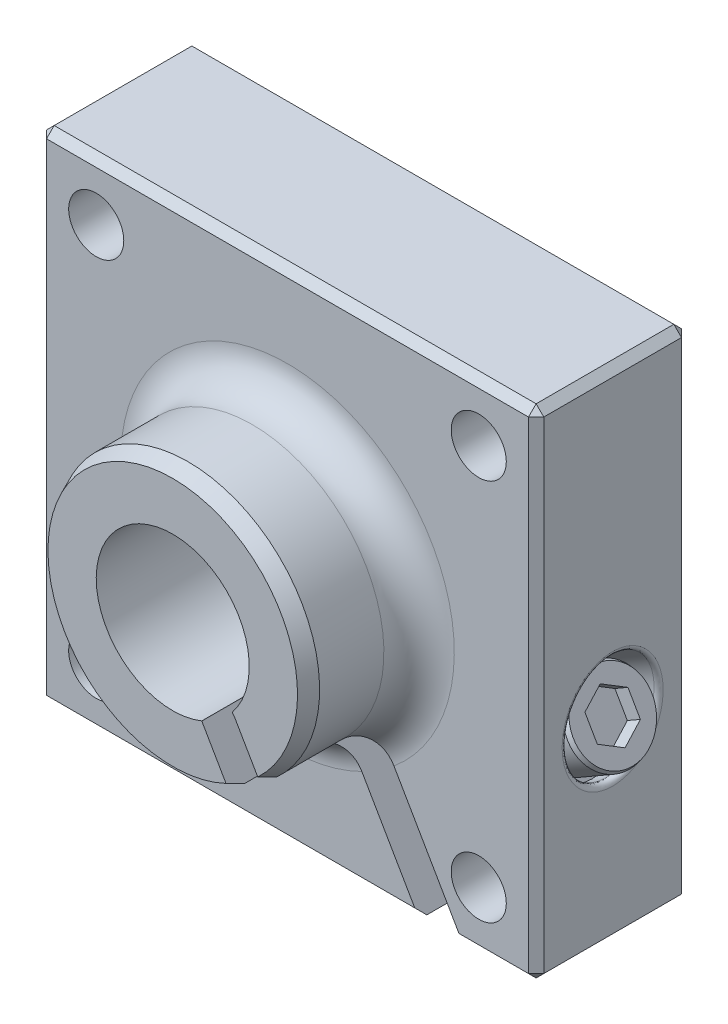
SolidWorks part; units mm, degrees
ref_plane "Front" through (0, 0, 0) normal (0, 0, 1) x (1, 0, 0)
ref_plane "Top" through (0, 0, 0) normal (0, 1, 0) x (1, 0, 0)
ref_plane "Right" through (0, 0, 0) normal (1, 0, 0) x (0, 0, -1)
sketch "Sketch1" plane through (0, 0, 0) normal (0, 0, 1) x (1, 0, 0)
  line L0 (-15.875, 0) -> (15.875, 0) construction
  line L1 (20.6375, -20.6375) -> (-20.6375, -20.6375)
  line L2 (20.6375, -20.6375) -> (20.6375, 20.6375)
  line L3 (20.6375, 20.6375) -> (-20.6375, 20.6375)
  line L4 (-20.6375, -20.6375) -> (-20.6375, 20.6375)
  line L5 (20.6375, -20.6375) -> (-20.6375, 20.6375) construction
  line L6 (20.6375, 20.6375) -> (-20.6375, -20.6375) construction
  line L7 (15.875, -15.875) -> (15.875, 15.875)
  line L8 (15.875, 15.875) -> (-15.875, 15.875)
  line L9 (-15.875, -15.875) -> (-15.875, 15.875)
  line L10 (15.875, -15.875) -> (-15.875, -15.875)
  circle A0 centre (15.875, 15.875) radius 2.286
  circle A1 centre (-15.875, 15.875) radius 2.286
  circle A2 centre (-15.875, -15.875) radius 2.286
  circle A3 centre (15.875, -15.875) radius 2.286
  circle A4 centre (0, 0) radius 6.35
  point P0 (0, 0)
  point P8 (0, 0)
  dimension "D1" = 4.7625
ref_plane "Plane1" through (0, 20.6375, 0) normal (0, 1, 0) x (1, 0, 0)
sketch "Sketch3" plane through (0, 20.6375, 0) normal (0, 1, 0) x (1, 0, 0)
  line L1 (20.6375, 0) -> (-20.6375, 0) construction
  line L2 (20.6375, 0) -> (20.6375, 12.7) construction
  line L3 (20.6375, 12.7) -> (-20.6375, 12.7) construction
  line L4 (-20.6375, 0) -> (-20.6375, 12.7) construction
  line L6 (20.6375, 12.7) -> (-20.6375, 0) construction
  line L8 (0, -9.525) -> (20.6375, -9.525) construction
  line L9 (0, 0) -> (0, -9.525) construction
  point P0 (0, 0)
  point P6 (0, 0)
  point P11 (0, -9.525)
  dimension "D1" = 41.275
sketch "Sketch4" plane through (0, 0, 0) normal (0, 0, 1) x (1, 0, 0)
  line L0 (20.6375, -20.6375) -> (20.6375, 20.6375) construction
  line L1 (20.6375, 20.6375) -> (-20.6375, 20.6375) construction
  line L2 (-20.6375, -20.6375) -> (-20.6375, 20.6375) construction
  line L3 (20.6375, -20.6375) -> (-20.6375, -20.6375) construction
  line L4 (20.6375, -20.6375) -> (20.6375, 20.6375)
  line L5 (20.6375, 20.6375) -> (-20.6375, 20.6375)
  line L6 (-20.6375, -20.6375) -> (-20.6375, 20.6375)
  line L7 (20.6375, -20.6375) -> (-20.6375, -20.6375)
  circle A0 centre (-15.875, -15.875) radius 2.286 construction
  circle A1 centre (15.875, -15.875) radius 2.286 construction
  circle A2 centre (15.875, 15.875) radius 2.286 construction
  circle A3 centre (-15.875, 15.875) radius 2.286 construction
  circle A4 centre (0, 0) radius 6.35 construction
  circle A5 centre (-15.875, -15.875) radius 2.286
  circle A6 centre (15.875, -15.875) radius 2.286
  circle A7 centre (15.875, 15.875) radius 2.286
  circle A8 centre (-15.875, 15.875) radius 2.286
  circle A9 centre (0, 0) radius 6.35
extrude "Boss-Extrude1" add sketch "Sketch4" against normal up to vertex (12.7 mm away) up to point (-20.6375, 20.6375, -12.7)
sketch "Sketch6" plane through (0, 0, 0) normal (0, 0, 1) x (1, 0, 0)
  line L4 (-20.6375, -20.6375) -> (20.6375, -20.6375)
  line L5 (20.6375, -20.6375) -> (20.6375, 20.6375)
  line L6 (20.6375, 20.6375) -> (-20.6375, 20.6375)
  line L7 (-20.6375, 20.6375) -> (-20.6375, -20.6375)
  line L8 (-20.6375, -20.6375) -> (20.6375, -20.6375)
  line L9 (20.6375, -20.6375) -> (20.6375, 20.6375)
  line L10 (20.6375, 20.6375) -> (-20.6375, 20.6375)
  line L11 (-20.6375, 20.6375) -> (-20.6375, -20.6375)
  circle A0 centre (0, 0) radius 6.35 construction
  circle A1 centre (0, 0) radius 6.35
  circle A2 centre (0, 0) radius 10.922
  circle M5 centre (0, 0) radius 6.35
  dimension "D2" = 4.572
extrude "Boss-Extrude2" add sketch "Sketch6" along normal up to vertex (9.525 mm away) contours A2 M5 region at (-10.6131, 0, 0) up to point (0, 20.6375, 9.525)
sketch "Sketch7" plane through (0, 0, 9.525) normal (0, 0, 1) x (1, 0, 0)
  line L0 (20.6375, -20.6375) -> (12.7635, -20.6375) construction
sketch "Sketch8" plane through (0, 0, 9.525) normal (0, 0, 1) x (1, 0, 0)
  line L0 (12.7635, -20.6375) -> (3.79, -5.0949) construction
  line L1 (20.6375, -20.6375) -> (-20.6375, -20.6375) construction
  line L2 (12.7635, -20.6375) -> (3.79, -5.0949) construction
  line L3 (11.3887, -21.4312) -> (2.4152, -5.8887)
  line L4 (14.1383, -19.8438) -> (5.1648, -4.3012)
  circle A0 centre (0, 0) radius 6.35 construction
  arc A1 (11.3887, -21.4312) -> (14.1383, -19.8438) centre (12.7635, -20.6375) ccw
  arc A2 (5.1648, -4.3012) -> (2.4152, -5.8887) centre (3.79, -5.0949) ccw
  point P7 (8.2767, -12.8662)
  point P12 (12.7635, -20.6375)
  dimension "D1" = 60
  dimension "D2" = 1.5875
  dimension "D3" = 7.874
extrude "Cut-Extrude1" cut sketch "Sketch8" against normal through all
chamfer "Chamfer1" distance 1.27 angle 24 1 edges at (-6.0915, 9.0655, 9.525) first distance on face at (-0.0325, 0.0484, 4.7625)
chamfer "Chamfer3" distance 0.635 angle 45 14 edges at (20.6375, 0, 0) (-20.6375, 20.6375, -6.35) (0, 20.6375, -12.7) (20.6375, 20.6375, -6.35) (-4.8535, -20.6375, -12.7) (-20.6375, 0, -12.7) (-20.6375, -20.6375, -6.35) (-20.6375, 0, 0) (0, 20.6375, 0) (17.4942, -20.6375, -12.7) (20.6375, 0, -12.7) (20.6375, -20.6375, -6.35) (-4.8535, -20.6375, 0) (17.4942, -20.6375, 0)
sketch "Sketch9" plane through (0, 0, 0) normal (0, 0, 1) x (1, 0, 0)
  line L0 (-20.0025, -20.6375) -> (20.6375, -20.6375) construction
  line L1 (4.3155, -13.7542) -> (20.6375, -4.3307) construction
  line L3 (20.6375, -0.9017) -> (20.6375, -7.7597)
  line L4 (20.6375, 20.0025) -> (20.6375, -20.0025) construction
  line L5 (20.6375, -7.7597) -> (20.0328, -7.7597) construction
  line L6 (20.6375, -6.4135) -> (20.6375, -2.2479) construction
  point P2 (20.6375, -4.3307)
  point P9 (20.6375, -0.9017)
  point P14 (39.6875, 98.1015)
  point P15 (-39.865, -39.6875)
  point P16 (20.6375, -4.3307)
  point P19 (20.6375, -4.3307)
  dimension "D2" = 12.8778
  dimension "D4" = 30
  dimension "D1" = 18.847
sketch "Sketch14" plane through (0, 0, -12.7) normal (0, 0, -1) x (-1, 0, 0)
  line L7 (-2.4152, -5.8887) -> (-10.5638, -20.0025)
  line L8 (-10.5638, -20.0025) -> (20.0025, -20.0025)
  line L9 (20.0025, -20.0025) -> (20.0025, 20.0025)
  line L10 (20.0025, 20.0025) -> (-20.0025, 20.0025)
  line L11 (-20.0025, 20.0025) -> (-20.0025, -20.0025)
  line L12 (-20.0025, -20.0025) -> (-14.2185, -20.0025)
  line L13 (-14.1383, -19.8438) -> (-5.1648, -4.3012)
  line L14 (-2.4152, -5.8887) -> (-10.5638, -20.0025)
  line L15 (-10.5638, -20.0025) -> (20.0025, -20.0025)
  line L16 (20.0025, -20.0025) -> (20.0025, 20.0025)
  line L17 (20.0025, 20.0025) -> (-20.0025, 20.0025)
  line L18 (-20.0025, 20.0025) -> (-20.0025, -20.0025)
  line L19 (-20.0025, -20.0025) -> (-14.2185, -20.0025)
  line L20 (-14.1383, -19.8438) -> (-5.1648, -4.3012)
  line L21 (-4.3155, -13.7542) -> (-20.6375, -4.3307) construction
  line L22 (-4.3155, -13.7542) -> (-20.6375, -4.3307) construction
  arc A3 (-14.1383, -19.8438) -> (-14.2185, -20.0025) centre (-12.7635, -20.6375) ccw
  arc A4 (-4.9353, -3.9957) -> (-5.1648, -4.3012) centre (-3.79, -5.0949) ccw
  arc A5 (-2.4078, -5.8758) -> (-4.9353, -3.9957) centre (0, 0) ccw
  arc A6 (-14.1383, -19.8438) -> (-14.2185, -20.0025) centre (-12.7635, -20.6375) ccw
  arc A7 (-4.9353, -3.9957) -> (-5.1648, -4.3012) centre (-3.79, -5.0949) ccw
  arc A8 (-2.4078, -5.8758) -> (-4.9353, -3.9957) centre (0, 0) ccw
  arc A10 (-2.4152, -5.8887) -> (-2.4078, -5.8758) centre (-3.79, -5.0949) ccw
  arc A11 (-2.4152, -5.8887) -> (-2.4078, -5.8758) centre (-3.79, -5.0949) ccw
  dimension "D1" = 0
ref_plane "Plane4" through (7.0346, -12.1843, 0) normal (0.5, -0.866, 0) x (-0.866, -0.5, 0)
sketch "Sketch15" plane through (20.6375, 0, 0) normal (1, 0, 0) x (0, 0, -1)
  line L0 (0, -4.3307) -> (12.7, -4.3307) construction
  line L1 (12.7, -13.7542) -> (12.7, -4.3307) construction
  line L2 (12.7, -6.35) -> (12.7, 6.35) construction
ref_plane "Plane5" through (13.6029, 7.8536, 0) normal (-0.866, -0.5, 0) x (0, 0, -1)
sketch "Sketch16" plane through (7.0346, -12.1843, 0) normal (0.5, -0.866, 0) x (-0.866, -0.5, 0)
  line L0 (-15.7072, 0) -> (-15.7072, 12.7) construction
  line L1 (-15.7072, 0) -> (-15.7072, 12.7) construction
  line L2 (-15.7072, 6.35) -> (7.8785, 6.35) construction
  dimension "D1" = 23.5857
sketch "Sketch17" plane through (20.6375, 0, 0) normal (1, 0, 0) x (0, 0, -1)
  line L0 (0, -7.7597) -> (18.9157, -7.7597) construction
  line L1 (0, -0.9017) -> (18.9157, -0.9017) construction
  point P6 (6.35, -4.3307)
sketch "Sketch18" plane through (13.6029, 7.8536, 0) normal (-0.866, -0.5, 0) x (0, 0, -1)
  circle A0 centre (6.35, 14.0692) radius 2.1463
  dimension "D1" = 4.2926
extrude "Cut-Extrude2" cut sketch "Sketch18" along normal up to vertex (18.847 mm away) and the other way blind 2.54 contours A0 region at (20.6375, -4.3307, -6.35) up to point (4.3155, -13.7542, -12.7)
sketch "Sketch19" plane through (13.6029, 7.8536, 0) normal (-0.866, -0.5, 0) x (0, 0, -1)
  circle A0 centre (6.35, 14.0692) radius 3.81
  dimension "D1" = 7.62
extrude "Cut-Extrude3" cut sketch "Sketch19" along normal blind 4.1656 and the other way through all
sketch "Sketch21" plane through (7.0346, -12.1843, 0) normal (0.5, -0.866, 0) x (-0.866, -0.5, 0)
  line L0 (-11.9226, 2.921) -> (-15.7072, 2.921) construction
  line L1 (-15.7072, 6.35) -> (7.8785, 6.35)
  line L2 (7.8785, 4.2672) -> (7.8785, 8.4328) construction
  line L3 (7.8785, 8.4328) -> (-11.9226, 8.4328)
  line L4 (-11.9226, 8.4328) -> (-11.9226, 9.779)
  line L5 (-11.9226, 9.779) -> (-15.7072, 9.779)
  line L6 (-15.7072, 0) -> (-15.7072, 12.7) construction
  line L7 (-15.7072, 0) -> (-15.7072, 12.7) construction
  line L8 (-15.7072, 9.779) -> (-15.7072, 2.921) construction
  line L9 (-11.9226, 4.2672) -> (-11.9226, 2.921) construction
  line L10 (7.8785, 4.2672) -> (-11.9226, 4.2672) construction
  line L11 (7.8785, 8.4328) -> (7.8785, 6.35)
  line L12 (-15.7072, 9.779) -> (-15.7072, 6.35)
  dimension "D1" = 4.1656
  dimension "D3" = 3.7846
  dimension "D2" = 6.858
revolve "Revolve2" add sketch "Sketch21" angle 360 about L1
sketch "Sketch22" plane through (13.6029, 7.8536, 0) normal (0.866, 0.5, 0) x (0, 0, -1)
  line L0 (6.35, -16.1315) -> (6.35, -12.007) construction
  line L1 (6.35, -16.1315) -> (8.1359, -15.1004)
  line L2 (8.1359, -15.1004) -> (8.1359, -13.0381)
  line L3 (8.1359, -13.0381) -> (6.35, -12.007)
  line L4 (6.35, -12.007) -> (4.5641, -13.0381)
  line L5 (4.5641, -13.0381) -> (4.5641, -15.1004)
  line L6 (4.5641, -15.1004) -> (6.35, -16.1315)
  circle A0 centre (6.35, -14.0692) radius 1.7859 construction
  dimension "HexSize" = 3.5719
extrude "Cut-Extrude4" cut sketch "Sketch22" against normal blind 1.2497
chamfer "Chamfer4" distance 0.381 angle 24 1 edges at (18.923, -1.3611, -6.35) first distance on face at (18.923, -1.3611, -6.35)
fillet "Fillet1" radius 0.381 1 edges at (20.6375, -8.7301, -6.35)
fillet "Fillet2" radius 2.921 1 edges at (-6.0915, 9.0655, 0)
equation "\"D1@Sketch1\"=(\"HT@Sketch1\"-\"CTChole@Sketch1\")/2"
equation "\"D1@Sketch3\"= \"LG@Sketch1\""
equation "\"D2@Sketch6\"=\"DiaHole@Sketch1\""
equation "\"D3@Sketch8\"=\"AngleDistance@Sketch7\""
equation "\"D2@Sketch9\"=\"AngleDistance@Sketch7\"*1.635484"
equation "\"D1@Sketch18\"=\"ThrdDia@Sketch9\"+.005"
equation "\"D1@Sketch19\"= \"HeadDia@Sketch9\"+.03"
equation "\"D1@Cut-Extrude3\"=\"ThrdDia@Sketch9\""
equation "\"D2@Sketch21\"=\"HeadDia@Sketch9\""
equation "\"D3@Sketch21\"=\"ThrdDia@Sketch9\"-.015"
equation "\"D1@Cut-Extrude4\"=\"ThrdDia@Sketch9\"*.30"
equation "\"D1@Sketch9\"=\"LG@Sketch1\"/2.19"
equation "\"D1@Sketch16\"=\"LG@Sketch1\"/1.75"
equation "\"D1@Sketch21\"=\"ThrdDia@Sketch9\""
